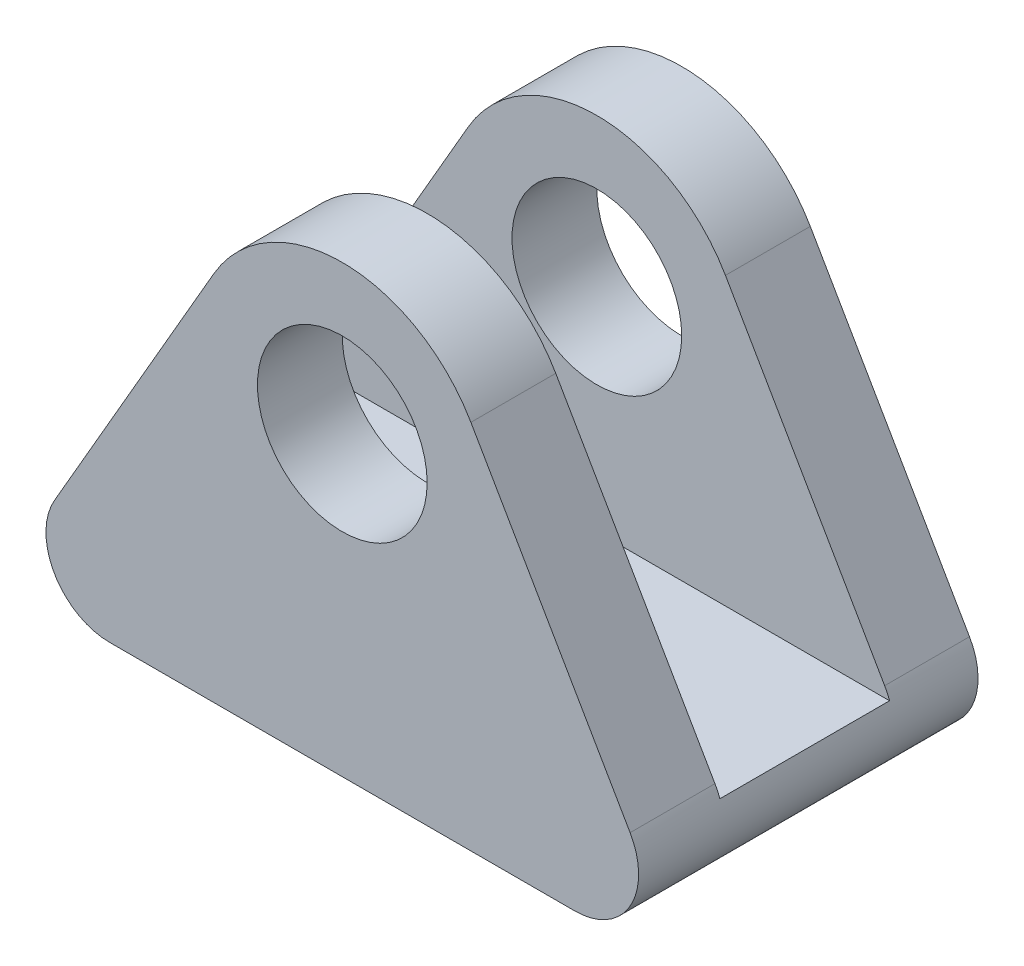
SolidWorks part; units mm, degrees
ref_plane "Front Plane" through (0, 0, 0) normal (0, 0, 1) x (1, 0, 0)
ref_plane "Top Plane" through (0, 0, 0) normal (0, 1, 0) x (1, 0, 0)
ref_plane "Right Plane" through (0, 0, 0) normal (1, 0, 0) x (0, 0, -1)
sketch "Sketch1" plane through (0, 0, 0) normal (0, 0, 1) x (1, 0, 0)
  line L0 (0, 4) -> (0, 7) construction
  line L1 (-6.0622, 3.5) -> (-16.1658, -14)
  line L2 (-16.1658, -14) -> (16.1658, -14)
  line L3 (16.1658, -14) -> (6.0622, 3.5)
  line L4 (6.0622, 3.5) -> (-6.0622, 3.5) construction
  line L5 (0, 0) -> (0, -14) construction
  line L6 (0, 3.5) -> (0, 4) construction
  line L7 (0, 0) -> (0, 3.5) construction
  circle A0 centre (0, 0) radius 4
  arc A1 (6.0622, 3.5) -> (-6.0622, 3.5) centre (0, 0) ccw
  dimension "D1" = 8
  dimension "D2" = 14
  dimension "D3" = 3
  dimension "D4" = 14
  dimension "D5" = 60
extrude "MainBody" add sketch "Sketch1" along normal blind 4
sketch "Sketch3" plane through (0, 0, 0) normal (0, 0, -1) x (-1, 0, 0)
  line L0 (-16.1658, -14) -> (-13.8564, -10)
  line L1 (-16.1658, -14) -> (-6.0622, 3.5) construction
  line L2 (-13.8564, -10) -> (13.8564, -10)
  line L3 (6.0622, 3.5) -> (16.1658, -14) construction
  line L4 (13.8564, -10) -> (16.1658, -14)
  line L5 (16.1658, -14) -> (-16.1658, -14) construction
  line L6 (16.1658, -14) -> (-16.1658, -14)
  dimension "D1" = 4
extrude "Boss-Extrude2" add sketch "Sketch3" along normal blind 8
ref_plane "BodyMidPlane" through (0, 0, -4) normal (0, 0, -1) x (-1, 0, 0)
mirror "Mirror2" about plane through (0, 0, -4) normal (0, 0, -1) of "MainBody"
fillet "Fillet1" radius 3 2 edges at (-16.1658, -14, -4) (16.1658, -14, -4)
